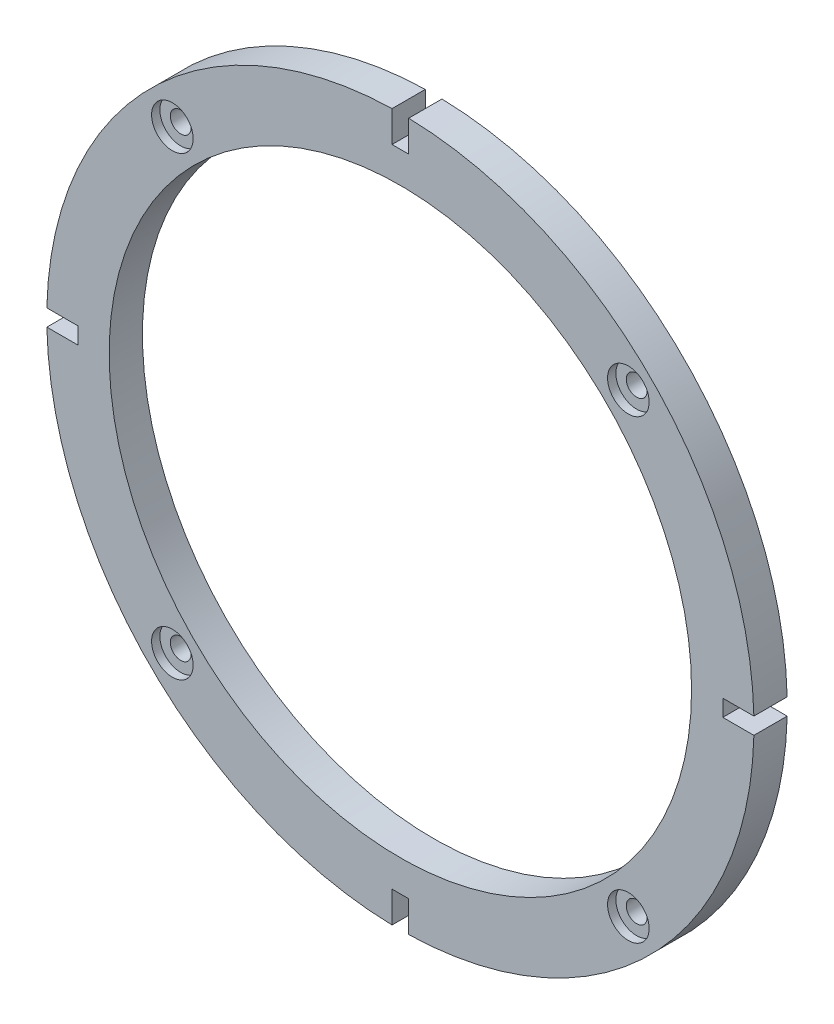
SolidWorks part; units mm, degrees
material "Stop 1060"
ref_plane "Płaszczyzna przednia" through (0, 0, 0) normal (0, 0, 1) x (1, 0, 0)
ref_plane "Płaszczyzna górna" through (0, 0, 0) normal (0, 1, 0) x (1, 0, 0)
ref_plane "Płaszczyzna prawa" through (0, 0, 0) normal (1, 0, 0) x (0, 0, -1)
sketch "Sketch1" plane through (0, 0, 0) normal (0, 0, 1) x (1, 0, 0)
  line L0 (84.9765, -2) -> (77.4996, -2)
  line L1 (-2, 77.4996) -> (2, 77.4996)
  line L2 (-2, 77.4996) -> (-2, 84.9765)
  line L4 (2, 84.9765) -> (2, 77.4996)
  line L5 (77.4996, 2) -> (84.9765, 2)
  line L6 (77.4996, 2) -> (77.4996, -2)
  line L7 (-2, -84.9765) -> (-2, -77.4996)
  line L8 (2, -77.4996) -> (2, -84.9765)
  line L9 (2, -77.4996) -> (-2, -77.4996)
  line L10 (-84.9765, 2) -> (-77.4996, 2)
  line L11 (-77.4996, -2) -> (-84.9765, -2)
  line L12 (-77.4996, -2) -> (-77.4996, 2)
  circle A0 centre (0, 0) radius 70
  arc A1 (-2, 84.9765) -> (-84.9765, 2) centre (0, 0) ccw
  arc A2 (-84.9765, -2) -> (-2, -84.9765) centre (0, 0) ccw
  arc A3 (2, -84.9765) -> (84.9765, -2) centre (0, 0) ccw
  arc A4 (84.9765, 2) -> (2, 84.9765) centre (0, 0) ccw
  point P6 (-2, 77.4996)
  point P7 (2, 77.4996)
  point P24 (0, 0)
  dimension "D1" = 170
  dimension "D2" = 140
  dimension "D3" = 77.4996
  dimension "D4" = 2
  dimension "D5" = 4
  dimension "D6" = 4
extrude "Boss-Extrude1" add sketch "Sketch1" along normal blind 8 contours A0 | A1 L10 L12 L11 A2 L7 L9 L8 A3 L0 L6 L5 A4 L4 L1 L2 region at (0, 0, 0)
sketch "Sketch2" plane through (0, 0, 0) normal (0, 0, -1) x (-1, 0, 0)
  line L0 (0, 0) -> (-73.6832, 73.6832) construction
  line L1 (0, 0) -> (0, 118.1493) construction
  circle A0 centre (-54.8008, 54.8008) radius 3.5
  arc A1 (-2, 84.9765) -> (-84.9765, 2) centre (0, 0) ccw construction
  circle A2 centre (54.8008, 54.8008) radius 3.5
  circle A3 centre (54.8008, -54.8008) radius 3.5
  circle A4 centre (-54.8008, -54.8008) radius 3.5
  point P18 (0, 0)
  dimension "D3" = 7
  dimension "D1" = 77.5
  dimension "D2" = 45
  dimension "D4" = 4
extrude "Cut-Extrude1" cut sketch "Sketch2" against normal blind 3 contours A0 | A4 | A3 | A2
sketch "Sketch3" plane through (0, 0, 0) normal (0, 0, -1) x (-1, 0, 0)
  circle A0 centre (-54.8008, 54.8008) radius 2.5
  circle A1 centre (54.8008, 54.8008) radius 2.5
  circle A2 centre (54.8008, -54.8008) radius 2.5
  circle A3 centre (-54.8008, -54.8008) radius 2.5
  point P12 (0, 0)
  dimension "D1" = 5
  dimension "D2" = 4
extrude "Cut-Extrude2" cut sketch "Sketch3" against normal blind 14
sketch "Sketch4" plane through (0, 0, 8) normal (0, 0, 1) x (1, 0, 0)
  circle A0 centre (-54.8008, 54.8008) radius 5
  circle A1 centre (54.8008, 54.8008) radius 5
  circle A2 centre (54.8008, -54.8008) radius 5
  circle A3 centre (-54.8008, -54.8008) radius 5
  point P12 (0, 0)
  dimension "D1" = 10
  dimension "D2" = 4
extrude "Cut-Extrude3" cut sketch "Sketch4" against normal blind 2
sketch "Sketch5" plane through (0, 0, 3) normal (0, 0, -1) x (-1, 0, 0)
  circle A0 centre (54.8008, -54.8008) radius 2.5
  circle A1 centre (54.8008, -54.8008) radius 3.5
extrude "Boss-Extrude2" add sketch "Sketch5" along normal blind 3
pattern_circular "CirPattern1" count 4 over 360 about axis through (0, 0, 0) along (0, 0, 1) of "Boss-Extrude2"
